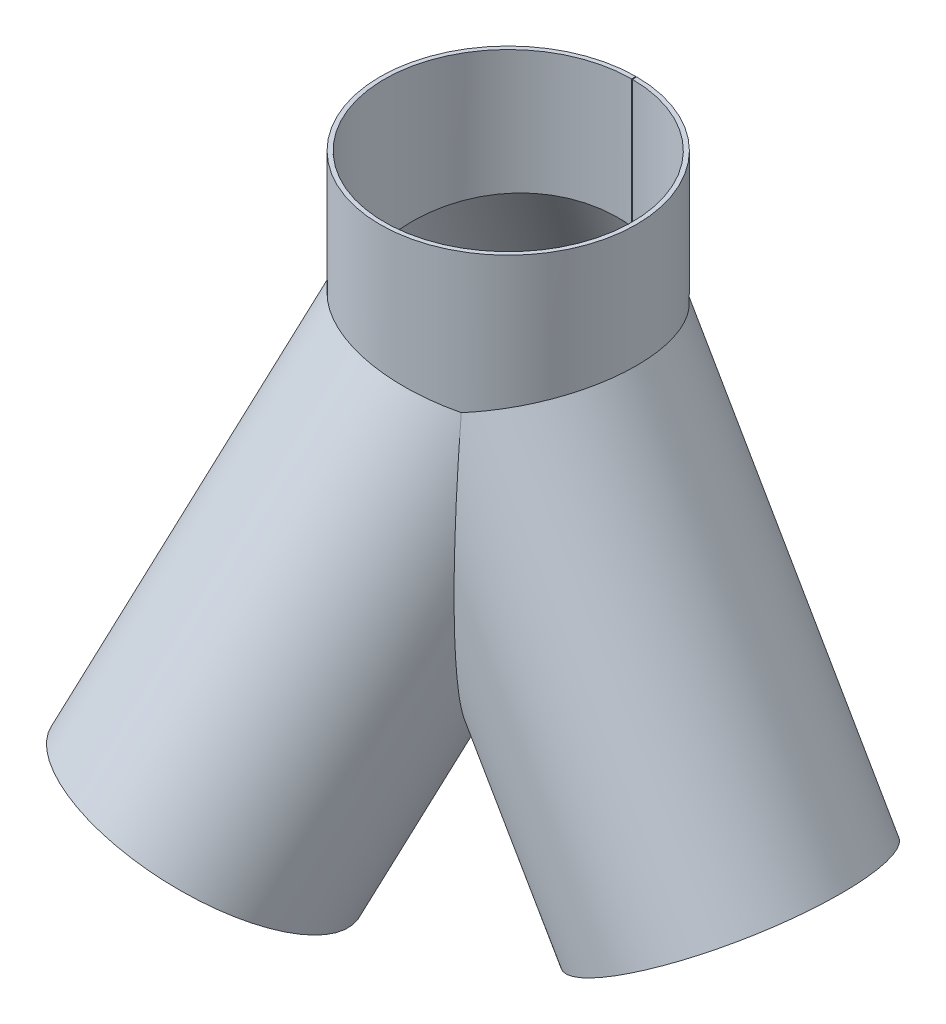
SolidWorks part; units mm, degrees
ref_plane "前视基准面" through (0, 0, 0) normal (0, 0, 1) x (1, 0, 0)
ref_plane "上视基准面" through (0, 0, 0) normal (0, 1, 0) x (1, 0, 0)
ref_plane "右视基准面" through (0, 0, 0) normal (1, 0, 0) x (0, 0, -1)
sketch "草图1" plane through (0, 0, 0) normal (0, 0, 1) x (1, 0, 0)
  line L0 (0, 0) -> (0, 220) construction
  line L1 (0, 0) -> (-356.0566, -450) construction
  line L2 (0, 0) -> (0, -540) construction
  line L3 (0, 0) -> (311.7691, -540) construction
  line L4 (-180, 0) -> (180, 0) construction
  line L5 (0, -540) -> (0, -546) construction
  line L6 (-180, 220) -> (180, 220) construction
  line L7 (155.8846, -630) -> (467.6537, -450) construction
  line L8 (467.6537, -450) -> (180, 48.2309) construction
  line L9 (180, 48.2309) -> (180, 220) construction
  line L10 (180, 48.2309) -> (0, 0) construction
  line L11 (0, 0) -> (-180, 48.2309) construction
  line L12 (0, -540) -> (0, 220)
  dimension "d" = 360
  dimension "t" = 6
  dimension "h" = 220
  dimension "hm" = 540
  dimension "β" = 30
sketch "草图2" plane through (0, 0, 0) normal (0, 1, 0) x (1, 0, 0)
  line L0 (0, 0) -> (90, 155.8846) construction
  line L1 (0, 0) -> (90, -155.8846) construction
  line L2 (0, 0) -> (-90, 155.8846) construction
  line L3 (0, 0) -> (-90, -155.8846) construction
  line L4 (-180, 0) -> (180, 0) construction
  circle A0 centre (0, 0) radius 180
  dimension "D1" = 60
  dimension "D2" = 60
  dimension "D3" = 60
  dimension "D4" = 60
extrude "拉伸-薄壁1" add sketch "草图2" along normal up to vertex (220 mm away) thin up to point (0, 220, 0) thin type one direction reverse wall 6
ref_plane "基准面1" through (311.7691, -540, 0) normal (0.5, -0.866, 0) x (0.866, 0.5, 0)
ref_axis "基准轴1" through (0, 262.5, 0) along (0, -1, 0)
sketch "草图3" plane through (311.7691, -540, 0) normal (0.5, -0.866, 0) x (0.866, 0.5, 0)
  circle A0 centre (0, 0) radius 180
extrude "拉伸-薄壁2" add sketch "草图3" against normal up to vertex (623.5383 mm away) separate body thin up to point (0, 0, 0) thin type one direction reverse wall 6
sketch "草图4" plane through (0, 0, 0) normal (0, 0, 1) x (1, 0, 0)
  line L0 (180, 48.2309) -> (-180, -48.2309)
  line L1 (180, 48.2309) -> (0, 0) construction
  dimension "D1" = 372.6994
extrude "切除-拉伸1" cut sketch "草图4" against normal through all and the other way through all
extrude "切除-拉伸14" cut sketch "草图4<3>" against normal through all and the other way through all flip side to cut
sketch "草图4<3>" plane through (0, 0, 0) normal (0, 0, 1) x (1, 0, 0) same geometry as "草图4"
ref_plane "基准面4" through (0, 0, 0) normal (-0.5, 0, -0.866) x (-0.866, 0, 0.5)
sketch "草图8" plane through (0, 0, 0) normal (-0.5, 0, -0.866) x (-0.866, 0, 0.5)
  line L0 (0, 220) -> (0, -540)
extrude "切除-拉伸10" cut sketch "草图8" against normal through all and the other way through all
ref_plane "基准面5" through (0, 0, 0) normal (0.5, 0, -0.866) x (-0.866, 0, -0.5)
sketch "草图9" plane through (0, 0, 0) normal (0.5, 0, -0.866) x (-0.866, 0, -0.5)
  line L0 (0, -540) -> (0, 220) construction
  line L1 (0, -540) -> (0, 220)
extrude "切除-拉伸13" cut sketch "草图9" against normal through all and the other way through all flip side to cut
ref_plane "基准面2" through (0, 0, 0) normal (0.866, 0, -0.5) x (-0.5, 0, -0.866)
sketch "草图6" plane through (0, 0, 0) normal (0.866, 0, -0.5) x (-0.5, 0, -0.866)
  line L0 (180, 48.2309) -> (-180, -48.2309)
  line L4 (-180, 0) -> (-60, 0) construction
  line L5 (-60, 0) -> (60, 0) construction
  line L6 (60, 0) -> (180, 0) construction
extrude "切除-拉伸12" cut sketch "草图6" against normal through all and the other way through all
ref_plane "基准面3" through (0, 0, 0) normal (-0.866, 0, -0.5) x (-0.5, 0, 0.866)
sketch "草图7" plane through (0, 0, 0) normal (-0.866, 0, -0.5) x (-0.5, 0, 0.866)
  line L0 (180, 48.2309) -> (-180, -48.2309)
  line L1 (-180, 0) -> (-60, 0) construction
  line L2 (-60, 0) -> (60, 0) construction
  line L3 (60, 0) -> (180, 0) construction
extrude "切除-拉伸11" cut sketch "草图7" against normal through all and the other way through all
extrude "切除-拉伸-薄壁1" cut sketch "草图1" against normal through all thin thin type mid plane wall 1
sketch "草图10" plane through (311.7691, -540, 0) normal (0.5, -0.866, 0) x (0.866, 0.5, 0)
  line L0 (0, 0) -> (-180, 0)
  circle A0 centre (0, 0) radius 180 construction
extrude "切除-拉伸-薄壁2" cut sketch "草图10" against normal through all thin thin type mid plane wall 1
pattern_circular "阵列(圆周)1" count 3 over 360 about axis through (0, 262.5, 0) along (0, -1, 0) of bodies 119 102
equation "\"D5@拉伸-薄壁1\" = \"t@草图1\""
equation "\"D5@拉伸-薄壁2\" = \"t@草图1\""
